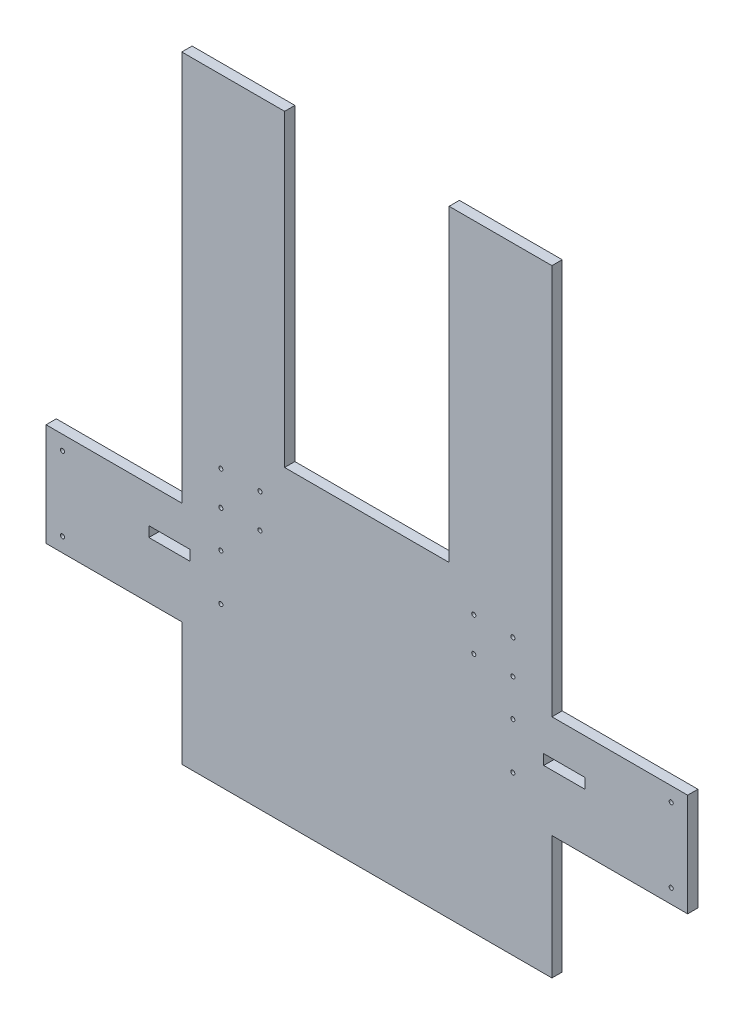
SolidWorks part; units mm, degrees
ref_plane "Front Plane" through (0, 0, 0) normal (0, 0, 1) x (1, 0, 0)
ref_plane "Top Plane" through (0, 0, 0) normal (0, 1, 0) x (1, 0, 0)
ref_plane "Right Plane" through (0, 0, 0) normal (1, 0, 0) x (0, 0, -1)
sketch "Sketch1" plane through (0, 0, 0) normal (0, 0, 1) x (1, 0, 0)
  line L0 (0, 150) -> (180, 150) construction
  line L1 (0, 0) -> (180, 0)
  line L2 (0, 0) -> (0, 300)
  line L3 (0, 300) -> (180, 300) construction
  line L4 (180, 0) -> (180, 300)
  line L5 (0, 300) -> (50, 300)
  line L6 (50, 300) -> (50, 150)
  line L7 (-66, 110) -> (0, 60) construction
  line L8 (0, 110) -> (-66, 110)
  line L9 (0, 110) -> (0, 60)
  line L10 (0, 60) -> (-66, 60)
  line L11 (-66, 110) -> (-66, 60)
  line L12 (0, 110) -> (-66, 60) construction
  line L13 (-33, 85) -> (-66, 85) construction
  line L14 (90, 150) -> (90, 0) construction
  line L15 (180, 110) -> (246, 110)
  line L16 (180, 110) -> (246, 60) construction
  line L17 (246, 110) -> (180, 60) construction
  line L18 (180, 60) -> (246, 60)
  line L19 (213, 85) -> (246, 85) construction
  line L20 (246, 110) -> (246, 60)
  line L21 (11, 117.5) -> (46, 117.5) construction
  line L22 (50, 150) -> (85, 150) construction
  line L23 (50, 150) -> (50, 110) construction
  line L24 (50, 110) -> (85, 110) construction
  line L25 (85, 150) -> (85, 110) construction
  line L26 (11, 150) -> (46, 150) construction
  line L27 (11, 150) -> (11, 110) construction
  line L28 (11, 110) -> (46, 110) construction
  line L29 (46, 150) -> (46, 110) construction
  line L30 (11, 134) -> (46, 134) construction
  line L31 (19, 150) -> (19, 110) construction
  line L32 (38, 150) -> (38, 110) construction
  line L33 (50, 150) -> (130, 150)
  line L34 (130, 300) -> (130, 150)
  line L35 (180, 300) -> (130, 300)
  circle A0 centre (19, 134) radius 1
  circle A1 centre (38, 134) radius 1
  circle A2 centre (19, 117.5) radius 1
  circle A3 centre (38, 117.5) radius 1
  circle A4 centre (161, 117.5) radius 1
  circle A5 centre (142, 117.5) radius 1
  circle A6 centre (142, 134) radius 1
  circle A7 centre (161, 134) radius 1
  point P7 (90, 150)
  dimension "D17" = 2
  dimension "D18" = 2
  dimension "D19" = 2
  dimension "D20" = 2
  dimension "D1" = 180
  dimension "D2" = 300
  dimension "D3" = 150
  dimension "D4" = 156
  dimension "D5" = 50
  dimension "D6" = 85
  dimension "D7" = 35
  dimension "D8" = 5
  dimension "D9" = 40
  dimension "D10" = 40
  dimension "D11" = 4
  dimension "D12" = 35
  dimension "D13" = 7.5
  dimension "D14" = 24
  dimension "D15" = 8
  dimension "D16" = 8
extrude "Boss-Extrude1" add sketch "Sketch1" along normal blind 5 contours L8 L11 L10 L2 | L2 L1 L4 | L20 L15 L4 L18 region at (90, 128.5731, 0) region at (-33, 85, 0) region at (213, 85, 0)
sketch "Sketch2" plane through (0, 0, 5) normal (0, 0, 1) x (1, 0, 0)
  line L0 (-66, 110) -> (-66, 60) construction
  line L1 (-66, 110) -> (-51, 110) construction
  line L2 (-66, 110) -> (-66, 60) construction
  line L3 (-66, 60) -> (-51, 60) construction
  line L4 (-51, 110) -> (-51, 60) construction
  line L5 (0, 60) -> (-66, 60) construction
  line L6 (-58, 110) -> (-58, 60) construction
  line L7 (90, 150) -> (90, 0) construction
  line L8 (0, 0) -> (180, 0) construction
  line L9 (50, 150) -> (130, 150) construction
  circle A0 centre (-58, 103) radius 1
  circle A1 centre (-58, 67) radius 1
  circle A2 centre (238, 67) radius 1
  circle A3 centre (238, 103) radius 1
  dimension "D4" = 2
  dimension "D5" = 7
  dimension "D7" = 2
  dimension "D1" = 50
  dimension "D2" = 15
  dimension "D3" = 7
  dimension "D6" = 7
extrude "Cut-Extrude1" cut sketch "Sketch2" against normal through all
sketch "Sketch3" plane through (0, 0, 5) normal (0, 0, 1) x (1, 0, 0)
  line L0 (-16, 92.5) -> (4, 87.5) construction
  line L1 (-16, 92.5) -> (4, 92.5)
  line L2 (-16, 92.5) -> (-16, 87.5)
  line L3 (-16, 87.5) -> (4, 87.5) construction
  line L4 (4, 92.5) -> (4, 87.5)
  line L5 (-16, 87.5) -> (4, 92.5) construction
  line L6 (19, 74.5) -> (19, 99.5) construction
  line L7 (-66, 110) -> (-66, 60) construction
  line L8 (0, 110) -> (-66, 110) construction
  line L9 (-16, 74.5) -> (4, 74.5) construction
  line L10 (-16, 87.5) -> (4, 87.5)
  line L11 (-16, 87.5) -> (-16, 37.5) construction
  line L12 (-16, 37.5) -> (4, 37.5) construction
  line L13 (4, 87.5) -> (4, 37.5) construction
  line L14 (4, 74.5) -> (19, 74.5) construction
  line L15 (90, 0) -> (90, 150) construction
  line L16 (0, 0) -> (180, 0) construction
  line L17 (50, 150) -> (130, 150) construction
  line L18 (196, 92.5) -> (196, 87.5)
  line L19 (196, 87.5) -> (176, 87.5)
  line L20 (176, 92.5) -> (176, 87.5)
  line L21 (196, 92.5) -> (176, 92.5)
  circle A0 centre (19, 77) radius 1
  circle A1 centre (19, 99.5) radius 1
  circle A2 centre (161, 77) radius 1
  circle A3 centre (161, 99.5) radius 1
  point P4 (-6, 90)
  dimension "D9" = 2
  dimension "D10" = 2
  dimension "D11" = 5
  dimension "D1" = 60
  dimension "D2" = 20
  dimension "D3" = 20
  dimension "D4" = 5
  dimension "D5" = 50
  dimension "D6" = 13
  dimension "D7" = 15
  dimension "D8" = 25
extrude "Cut-Extrude2" cut sketch "Sketch3" against normal through all
